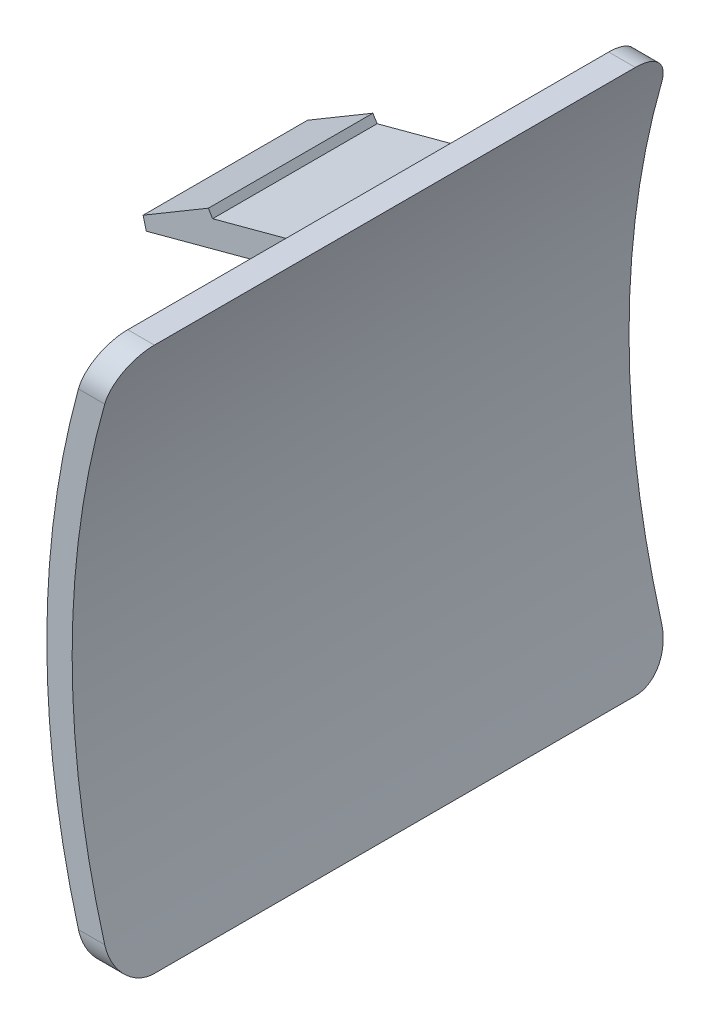
SolidWorks part; units mm, degrees
ref_plane "Спереди" through (0, 0, 0) normal (0, 0, 1) x (1, 0, 0)
ref_plane "Сверху" through (0, 0, 0) normal (0, 1, 0) x (1, 0, 0)
ref_plane "Справа" through (0, 0, 0) normal (1, 0, 0) x (0, 0, -1)
sketch "Эскиз1" plane through (0, 0, 0) normal (0, 0, 1) x (1, 0, 0)
  line L0 (0, 43) -> (0, 0) construction
  line L1 (0, 43) -> (-2.1055, 43)
  line L2 (0, 0) -> (-2.1055, 0)
  arc A0 (0, 0) -> (0, 43) centre (64.2857, 21.5) cw
  arc A1 (-2.1055, 0) -> (-2.1055, 43) centre (64.2857, 21.5) cw
  arc A3 (-1.8967, -0.6344) -> (-1.8967, 43.6344) centre (64.2857, 21.5) cw construction
  dimension "D1" = 3.5
  dimension "D2" = 43
  dimension "D3" = 2
extrude "Бобышка-Вытянуть1" add sketch "Эскиз1" against normal blind 22 and the other way blind 22
fillet "Скругление1" radius 3 4 edges at (-1.0528, 0, 22) (-1.0528, 0, -22) (-1.0528, 43, -22) (-1.0528, 43, 22)
sketch "Эскиз2" plane through (0, 0, 0) normal (0, 0, 1) x (1, 0, 0)
  line L0 (-2.1055, 43) -> (-14.3771, 43) construction
  line L1 (-2.1055, 43) -> (-7.9011, 41.4471)
  line L2 (-7.9011, 41.4471) -> (-8.237, 42)
  line L3 (-8.237, 42) -> (-13.3975, 38.939)
  line L4 (-13.3975, 38.939) -> (-13.1387, 37.9731)
  line L5 (-13.1387, 37.9731) -> (-2.7939, 40.745)
  line L6 (-2.1055, 43) -> (-2.7939, 40.745)
  arc A0 (-2.1055, 43) -> (-3.0032, 40) centre (64.2857, 21.5) ccw construction
  dimension "D1" = 6
  dimension "D2" = 12
  dimension "D3" = 6
  dimension "D4" = 15
  dimension "D5" = 2
  dimension "D6" = 2
  dimension "D7" = 1
extrude "Бобышка-Вытянуть2" add sketch "Эскиз2" along normal blind 6.5 and the other way blind 6.5
sketch "Эскиз3" plane through (0, 0, 0) normal (0, 0, 1) x (1, 0, 0)
  line L0 (-2.1055, 0) -> (-8, 0)
  line L1 (-8, 0) -> (-8, -6)
  line L2 (-8, -6) -> (-10, -6)
  line L3 (-10, -6) -> (-10, 2)
  line L4 (-10, 2) -> (-2.7202, 2)
  line L5 (-2.1055, 0) -> (-2.7202, 2)
  arc A0 (-3.0032, 3) -> (-2.1055, 0) centre (64.2857, 21.5) ccw construction
  dimension "D1" = 10
  dimension "D2" = 2
  dimension "D3" = 6
  dimension "D4" = 2
extrude "Бобышка-Вытянуть3" add sketch "Эскиз3" along normal blind 14 and the other way blind 14
sketch "Эскиз4" plane through (0, 0, 22) normal (0, 0, 1) x (1, 0, 0)
  line L0 (-5.5, 21.5) -> (-27.7328, 21.5) construction
  line L1 (-5.148, 14.5) -> (-9.5, 16)
  line L2 (-9.5, 16) -> (-9.5, 19.0505)
  line L3 (-5.5, 21.5) -> (-7.5, 21.5)
  line L4 (-5.148, 28.5) -> (-9.5, 27)
  line L5 (-9.5, 23.9495) -> (-9.5, 27)
  line L6 (-5.148, 28.5) -> (-5.5, 21.5)
  line L7 (-5.148, 14.5) -> (-5.5, 21.5)
  arc A0 (-3.0032, 40) -> (-3.0032, 3) centre (64.2857, 21.5) ccw construction
  arc A1 (-9.5, 19.0505) -> (-9.5, 23.9495) centre (-10, 21.5) ccw
  arc M1 (-3.0032, 40) -> (-3.0032, 3) centre (64.2857, 21.5) ccw
  dimension "D5" = 2.5
  dimension "D1" = 2
  dimension "D2" = 4
  dimension "D3" = 11
  dimension "D4" = 14
extrude "Бобышка-Вытянуть4" [suppressed] add sketch "Эскиз4" against normal blind 2 contours A1 L3 L4 L5 M1 | A1 L2 L1 L3 M1
mirror "Зеркальное отражение1" [suppressed] about plane through (0, 0, 0) normal (0, 0, 1)
